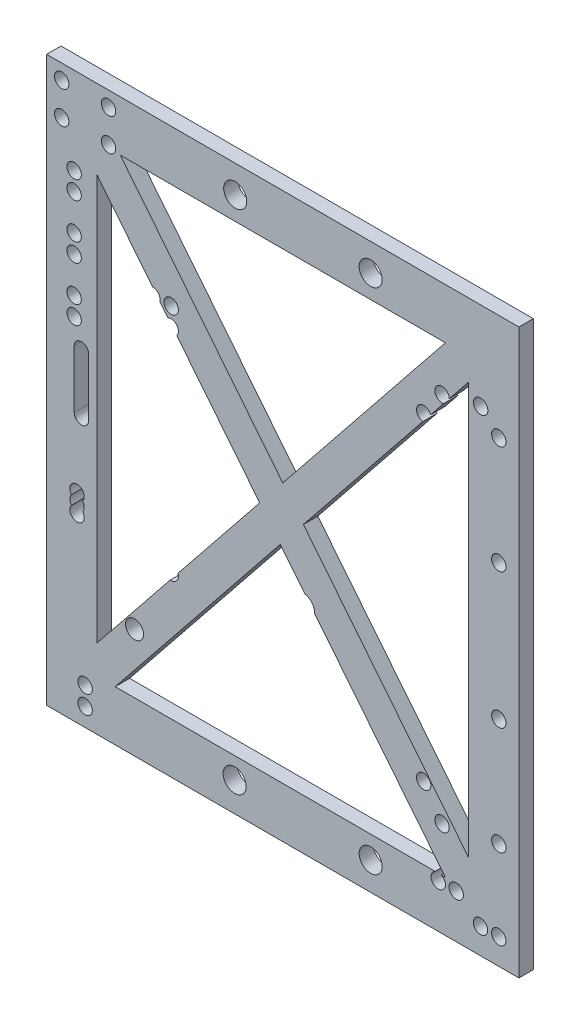
SolidWorks part; units mm, degrees
ref_plane "Front Plane" through (0, 0, 0) normal (0, 0, 1) x (1, 0, 0)
ref_plane "Top Plane" through (0, 0, 0) normal (0, 1, 0) x (1, 0, 0)
ref_plane "Right Plane" through (0, 0, 0) normal (1, 0, 0) x (0, 0, -1)
sketch "Sketch3" plane through (0, 0, 0) normal (0, 0, 1) x (1, 0, 0)
  line L0 (-58.532, 67.237) -> (-58.532, 10.995)
  line L1 (-65.532, 78.232) -> (0, 78.232)
  line L2 (-65.532, 78.232) -> (-65.532, 0)
  line L3 (-65.532, 0) -> (0, 0)
  line L4 (0, 78.232) -> (0, 0)
  line L5 (-56.0191, 7) -> (-10.2051, 7)
  line L6 (-7, 68.0998) -> (-7, 10.995)
  line L8 (-59.706, 45.116) -> (-59.706, 37.116)
  line L9 (-58.532, 71.232) -> (-7, 7) construction
  line L10 (-7, 71.232) -> (-58.532, 7) construction
  line L11 (-55.3269, 71.232) -> (-32.766, 43.111)
  line L12 (-58.532, 67.237) -> (-35.9711, 39.116)
  line L13 (-56.0191, 7) -> (-33.1121, 35.5524)
  line L14 (-58.532, 10.995) -> (-35.9711, 39.116)
  line L15 (-58.532, 71.232) -> (-58.532, 7) construction
  line L16 (-58.532, 7) -> (-7, 7) construction
  line L17 (-33.1121, 35.5524) -> (-10.2051, 7)
  line L18 (-32.766, 43.111) -> (-10.2051, 71.232)
  line L19 (-29.907, 39.5474) -> (-7, 10.995)
  line L20 (-29.907, 39.5474) -> (-7, 68.0998)
  line L21 (-58.532, 71.232) -> (-7, 71.232) construction
  line L22 (-55.3269, 71.232) -> (-10.2051, 71.232)
  line L23 (-7, 71.232) -> (-7, 7) construction
  line L25 (-61.706, 37.116) -> (-61.706, 45.116)
  circle A0 centre (-61.722, 66.169) radius 1
  circle A1 centre (-61.722, 63.629) radius 1
  circle A2 centre (-61.722, 58.669) radius 1
  circle A3 centre (-61.722, 56.129) radius 1
  circle A4 centre (-61.722, 51.169) radius 1
  circle A6 centre (-63.448, 76.164) radius 1
  circle A7 centre (-63.448, 71.664) radius 1
  circle A8 centre (-56.948, 71.664) radius 1
  circle A9 centre (-56.948, 76.164) radius 1
  circle A10 centre (-39.37, 74.422) radius 1.6
  circle A11 centre (-20.574, 74.422) radius 1.6
  circle A12 centre (-5.3091, 66.04) radius 1
  circle A13 centre (-2.794, 63.504) radius 1
  circle A14 centre (-2.794, 48.514) radius 1
  circle A15 centre (-2.794, 29.718) radius 1
  circle A16 centre (-2.794, 14.728) radius 1
  circle A17 centre (-2.799, 3.556) radius 1
  circle A18 centre (-5.339, 3.556) radius 1
  circle A19 centre (-8.7009, 6.096) radius 1
  circle A20 centre (-11.2009, 6.096) radius 1
  circle A21 centre (-20.574, 3.8909) radius 1.6
  circle A22 centre (-39.4509, 4.064) radius 1.6
  circle A23 centre (-60.198, 5.075) radius 1
  circle A24 centre (-60.198, 2.535) radius 1
  circle A25 centre (-61.32, 25.146) radius 1
  circle A26 centre (-61.32, 26.416) radius 1
  circle A27 centre (-61.32, 27.686) radius 1
  arc A28 (-61.706, 37.116) -> (-59.706, 37.116) centre (-60.706, 37.116) ccw
  arc A32 (-59.706, 45.116) -> (-61.706, 45.116) centre (-60.706, 45.116) ccw
  circle A33 centre (-61.722, 48.629) radius 1
  circle A34 centre (-48.255, 56.627) radius 1
  circle A35 centre (-13.213, 17.018) radius 1
  circle A36 centre (-10.668, 13.208) radius 1
  circle A37 centre (-48.26, 24.628) radius 1
  arc A39 (-47.4775, 53.4581) -> (-48.7004, 54.9823) centre (-48.255, 54.087) ccw
  arc A40 (-49.825, 56.3841) -> (-50.8218, 57.6266) centre (-50.795, 56.627) ccw
  circle A41 centre (-13.203, 61.214) radius 1
  circle A42 centre (-10.668, 64.77) radius 1
  circle A43 centre (-29.959, 29.718) radius 1.6
  circle A44 centre (-53.34, 15.24) radius 1.25
  dimension "D2" = 2
  dimension "D3" = 3.2
  dimension "D8" = 2.5
  dimension "D9" = 2
  dimension "D1" = 7
  dimension "D4" = 2.5
  dimension "D5" = 2.5
  dimension "D6" = 2.5
extrude "Boss-Extrude10" add sketch "Sketch3" along normal blind 2 contours L4 L1 L2 L3 A44 A43 L17 L5 A20 L13 A42 L20 L6 L19 A41 A40 L12 A39 L14 A37 L0 A36 A35 A34 A33 A32 L8 A28 L25 A27 A26 A25 region at (-32.422, 39.1083, 0)
sketch3d "3DSketch1"
  line L0 (0, 0, 2) -> (0, 0, 0) construction
  line L2 (-20.574, 0, 0) -> (-20.574, 0, 2)
  line L3 (-65.532, 0, 0) -> (0, 0, 0) construction
  line L4 (-65.532, 0, 2) -> (0, 0, 2) construction
  dimension "D1" = 20.574
ref_plane "Plane1" through (0, 39.116, 0) normal (0, 1, 0) x (1, 0, 0)
sketch "Sketch5" plane through (0, 0, 0) normal (0, -1, 0) x (1, 0, 0)
  line L0 (-20.574, 2) -> (-20.574, 0)
  line L1 (-39.454, 2) -> (-39.454, 0)
  line L2 (-65.532, 2) -> (0, 2) construction
  line L3 (36.0426, 0) -> (-36.0426, 0) construction
  line L4 (-39.454, 1) -> (-20.574, 1) construction
  line L9 (-26.2023, 4.5) -> (-27.6082, 6.935)
  line L10 (-27.6082, 6.935) -> (-30.4198, 6.935)
  line L11 (-33.014, 1.9998) -> (-25.014, 1.9998)
  line L12 (-30.014, 2) -> (-30.014, 7) construction
  line L13 (-25.014, 1.9998) -> (-25.014, 4.5)
  line L14 (-33.014, 1.9998) -> (-33.014, 4.5)
  line L15 (-25.014, 1.9998) -> (-25.014, 4.5)
  line L16 (-33.014, 1.9998) -> (-33.014, 4.5)
  line L17 (-30.4198, 6.935) -> (-31.8257, 4.5)
  line L18 (-31.8257, 4.5) -> (-30.4198, 2.065)
  line L19 (-30.4198, 2.065) -> (-27.6082, 2.065)
  line L20 (-27.6082, 2.065) -> (-26.2023, 4.5)
  arc A2 (-33.014, 4.5) -> (-25.014, 4.5) centre (-29.014, 4.5) cw
  circle A3 centre (-29.014, 4.5) radius 2.435 construction
  dimension "D2" = 8
  dimension "D3" = 2.5
  dimension "D4" = 4.87
  dimension "D1" = 18.88
